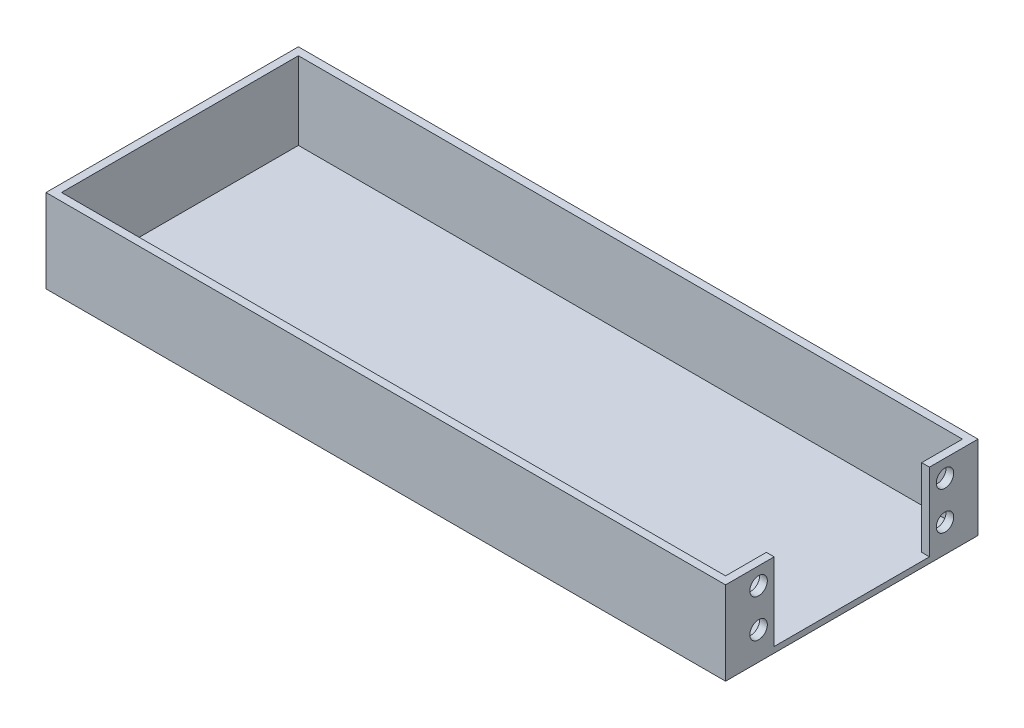
SolidWorks part; units mm, degrees
ref_plane "Спереди" through (0, 0, 0) normal (0, 0, 1) x (1, 0, 0)
ref_plane "Сверху" through (0, 0, 0) normal (0, 1, 0) x (1, 0, 0)
ref_plane "Справа" through (0, 0, 0) normal (1, 0, 0) x (0, 0, -1)
sketch "Эскиз1" plane through (0, 0, 0) normal (0, 1, 0) x (1, 0, 0)
  line L1 (-87.5, -32.5) -> (87.5, -32.5)
  line L2 (-87.5, -32.5) -> (-87.5, 32.5)
  line L3 (-87.5, 32.5) -> (87.5, 32.5)
  line L4 (87.5, -32.5) -> (87.5, 32.5)
  line L5 (-87.5, -32.5) -> (87.5, 32.5) construction
  line L6 (-87.5, 32.5) -> (87.5, -32.5) construction
  point P0 (0, 0)
  dimension "D1" = 175
  dimension "D2" = 65
extrude "Бобышка-Вытянуть1" add sketch "Эскиз1" along normal blind 1.5
sketch "Эскиз3" plane through (0, 1.5, 0) normal (0, 1, 0) x (1, 0, 0)
  line L5 (-87.5, -32.5) -> (87.5, -32.5)
  line L6 (-87.5, -32.5) -> (-87.5, 32.5)
  line L7 (-87.5, 32.5) -> (87.5, 32.5)
  line L8 (85.5, -30.5) -> (85.5, 30.5)
  line L9 (85.5, 30.5) -> (-85.5, 30.5)
  line L10 (-85.5, 30.5) -> (-85.5, -30.5)
  line L11 (-85.5, -30.5) -> (85.5, -30.5)
  line L12 (85.5, -30.5) -> (85.5, 30.5)
  line L13 (85.5, 30.5) -> (-85.5, 30.5)
  line L14 (-85.5, 30.5) -> (-85.5, -30.5)
  line L15 (-85.5, -30.5) -> (85.5, -30.5)
  line L16 (87.5, -32.5) -> (87.5, 32.5)
  line L17 (-87.5, -32.5) -> (87.5, 32.5) construction
  line L18 (-87.5, 32.5) -> (87.5, -32.5) construction
  point P0 (0, 0)
  dimension "D1" = 2
extrude "Бобышка-Вытянуть2" add sketch "Эскиз3" along normal blind 20
sketch "Эскиз4" plane through (87.5, 0, 0) normal (1, 0, 0) x (0, 0, -1)
  line L7 (-32.5, 21.5) -> (32.5, 21.5) construction
  line L8 (-20, 21.5) -> (20, 21.5)
  line L9 (-20, 21.5) -> (-20, 1.5)
  line L10 (-20, 1.5) -> (20, 1.5)
  line L11 (20, 21.5) -> (20, 1.5)
  line L12 (-32.5, 21.5) -> (-32.5, 0) construction
  dimension "D1" = 40
  dimension "D2" = 20
  dimension "D3" = 12.5
extrude "Вырез-Вытянуть1" cut sketch "Эскиз4" against normal blind 2
sketch "Эскиз5" plane through (0, 1.5, 0) normal (0, 1, 0) x (1, 0, 0)
  line L1 (87.5, 20) -> (57.5, 20)
  line L2 (87.5, 20) -> (87.5, -20)
  line L3 (87.5, -20) -> (57.5, -20)
  line L4 (57.5, 20) -> (57.5, -20)
  dimension "D1" = 30
  dimension "D2" = 40
sketch "Эскиз6" plane through (87.5, 0, 0) normal (1, 0, 0) x (0, 0, -1)
  line L0 (-32.5, 21.5) -> (-20, 21.5) construction
  line L1 (-20, 21.5) -> (-20, 1.5) construction
  circle A0 centre (-24, 17.05) radius 2.25
  circle A1 centre (-24, 7.25) radius 2.25
  dimension "D1" = 4.5
  dimension "D3" = 4.5
  dimension "D5" = 4
  dimension "D2" = 4.45
  dimension "D4" = 14.25
  dimension "D6" = 4
extrude "Вырез-Вытянуть2" cut sketch "Эскиз6" against normal blind 2
ref_plane "Плоскость2" through (0, 0, 0) normal (0, 0, -1) x (-1, 0, 0)
mirror "Зеркальное отражение2" about plane through (0, 0, 0) normal (0, 0, -1) of "Вырез-Вытянуть2"
